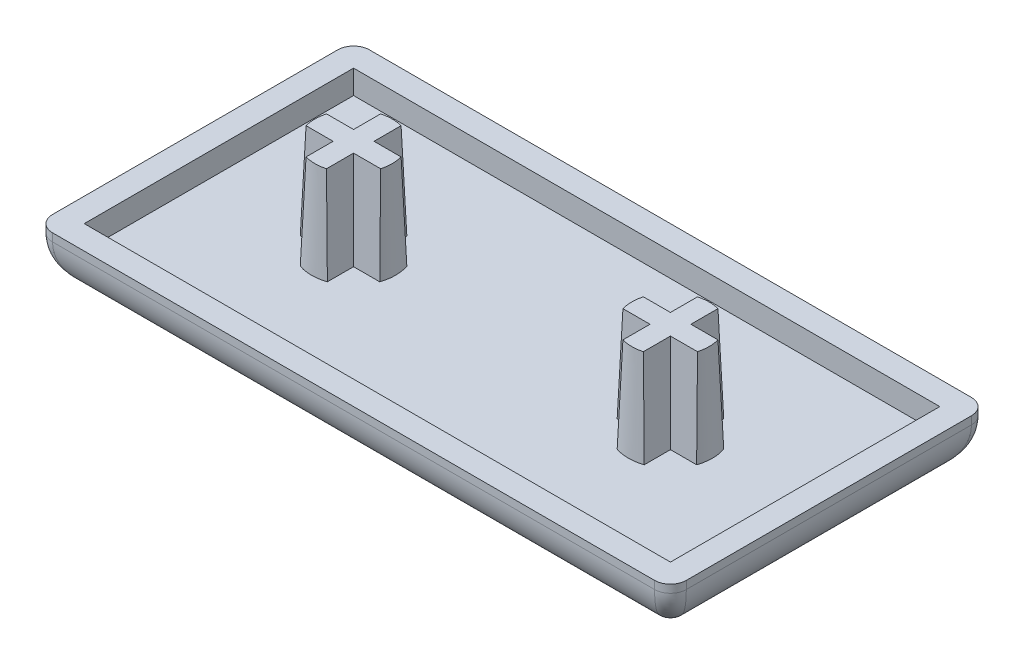
SolidWorks part; units mm, degrees
ref_plane "前视基准面" through (0, 0, 0) normal (0, 0, 1) x (1, 0, 0)
ref_plane "上视基准面" through (0, 0, 0) normal (0, 1, 0) x (1, 0, 0)
ref_plane "右视基准面" through (0, 0, 0) normal (1, 0, 0) x (0, 0, -1)
sketch "草图1" plane through (0, 0, 0) normal (0, 1, 0) x (1, 0, 0)
  line L1 (-20, -10) -> (20, -10)
  line L2 (-20, -10) -> (-20, 10)
  line L3 (-20, 10) -> (20, 10)
  line L4 (20, -10) -> (20, 10)
  line L5 (-20, -10) -> (20, 10) construction
  line L6 (-20, 10) -> (20, -10) construction
  point P0 (0, 0)
  dimension "D1" = 40
  dimension "D2" = 20
extrude "凸台-拉伸1" add sketch "草图1" along normal blind 2
sketch "草图2" plane through (0, 2, 0) normal (0, 1, 0) x (1, 0, 0)
  line L0 (-18.5, 8.5) -> (-18.5, -8.5)
  line L1 (-18.5, -8.5) -> (18.5, -8.5)
  line L2 (18.5, -8.5) -> (18.5, 8.5)
  line L3 (18.5, 8.5) -> (-18.5, 8.5)
  line L4 (20, -10) -> (20, 10)
  line L5 (20, 10) -> (-20, 10)
  line L6 (-20, 10) -> (-20, -10)
  line L7 (-20, -10) -> (20, -10)
  line L8 (20, -10) -> (20, 10)
  line L9 (20, 10) -> (-20, 10)
  line L10 (-20, 10) -> (-20, -10)
  line L11 (-20, -10) -> (20, -10)
  dimension "D1" = 0
  dimension "D2" = 1.5
extrude "凸台-拉伸2" add sketch "草图2" along normal blind 1.5
fillet "圆角1" radius 1 4 edges at (-20, 1.75, -10) (-20, 1.75, 10) (20, 1.75, 10) (20, 1.75, -10)
fillet "圆角2" radius 3 8 edges at (19.7071, 0, -9.7071) (20, 0, 0) (19.7071, 0, 9.7071) (0, 0, 10) (-19.7071, 0, 9.7071) (-20, 0, 0) (-19.7071, 0, -9.7071) (0, 0, -10)
sketch "草图3" plane through (0, 2, 0) normal (0, 1, 0) x (1, 0, 0)
  line L1 (-9.145, 0.855) -> (-7.4917, 0.855)
  line L2 (-10.855, 0.855) -> (-10.855, 2.5083)
  line L3 (-10.855, -2.5083) -> (-10.855, -0.855)
  line L4 (9.145, 0.855) -> (9.145, 2.5083)
  line L5 (-9.145, -2.5083) -> (-9.145, -0.855)
  line L6 (7.4917, -0.855) -> (9.145, -0.855)
  line L7 (10.855, 0.855) -> (12.5083, 0.855)
  line L8 (-12.5083, -0.855) -> (-10.855, -0.855)
  line L9 (-9.145, 0.855) -> (-9.145, 2.5083)
  line L10 (-12.5083, 0.855) -> (-10.855, 0.855)
  line L11 (-9.145, -0.855) -> (-7.4917, -0.855)
  line L12 (10.855, -0.855) -> (12.5083, -0.855)
  line L13 (10.855, -2.5083) -> (10.855, -0.855)
  line L14 (7.4917, 0.855) -> (9.145, 0.855)
  line L15 (9.145, -2.5083) -> (9.145, -0.855)
  line L16 (10.855, 0.855) -> (10.855, 2.5083)
  arc A0 (-12.5083, 0.855) -> (-12.5083, -0.855) centre (-10, 0) ccw
  arc A1 (-9.145, 2.5083) -> (-10.855, 2.5083) centre (-10, 0) ccw
  arc A2 (-7.4917, -0.855) -> (-7.4917, 0.855) centre (-10, 0) ccw
  arc A3 (-10.855, -2.5083) -> (-9.145, -2.5083) centre (-10, 0) ccw
  arc A4 (7.4917, 0.855) -> (7.4917, -0.855) centre (10, 0) ccw
  arc A5 (9.145, -2.5083) -> (10.855, -2.5083) centre (10, 0) ccw
  arc A6 (12.5083, -0.855) -> (12.5083, 0.855) centre (10, 0) ccw
  arc A7 (10.855, 2.5083) -> (9.145, 2.5083) centre (10, 0) ccw
extrude "凸台-拉伸3" add sketch "草图3" along normal blind 6 draft 2
